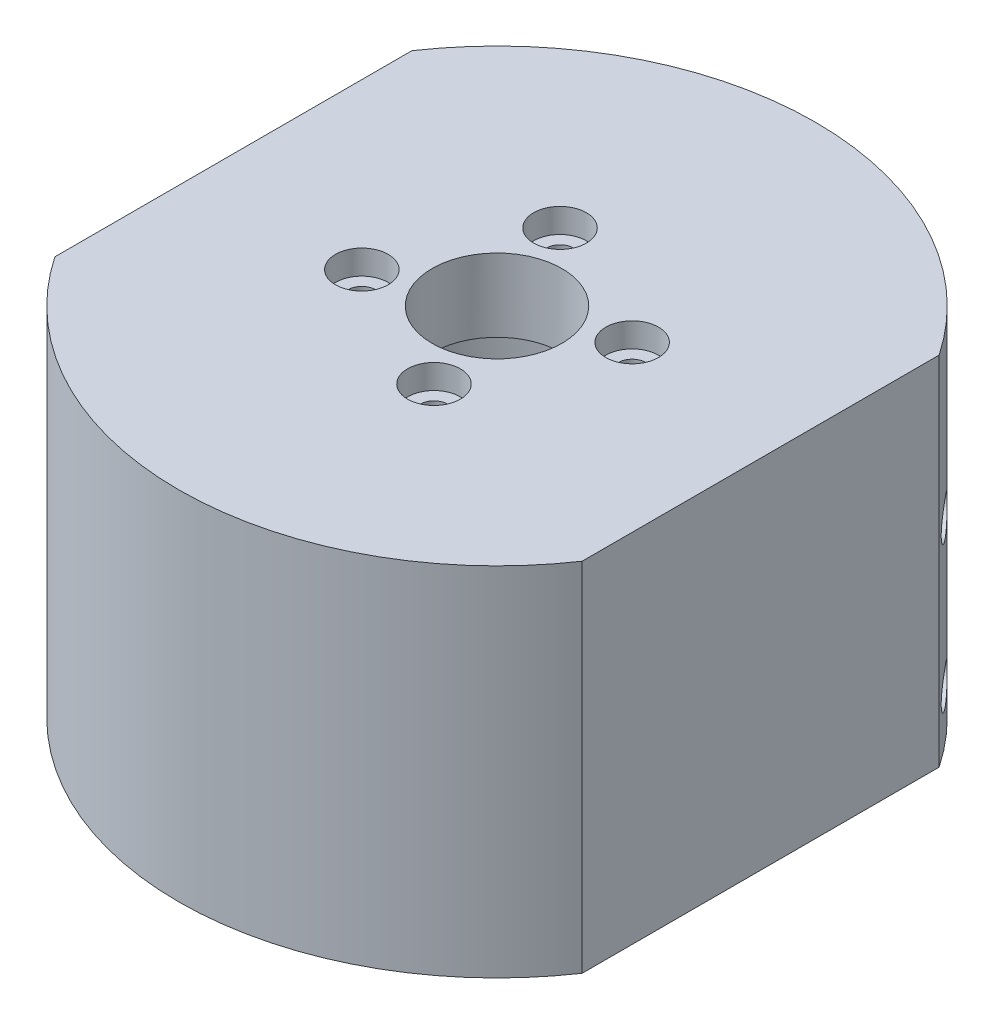
SolidWorks part; units mm, degrees
ref_plane "Front Plane" through (0, 0, 0) normal (0, 0, 1) x (1, 0, 0)
ref_plane "Top Plane" through (0, 0, 0) normal (0, 1, 0) x (1, 0, 0)
ref_plane "Right Plane" through (0, 0, 0) normal (1, 0, 0) x (0, 0, -1)
sketch "Sketch1" plane through (0, 0, 0) normal (0, 1, 0) x (1, 0, 0)
  line L0 (-32.5, 20.1696) -> (-32.5, -20.1696)
  line L1 (32.5, 20.1696) -> (32.5, -20.1696)
  line L2 (-32.5, 0) -> (32.5, 0) construction
  arc A0 (-32.5, -20.1696) -> (32.5, -20.1696) centre (0, 0) ccw
  arc A1 (32.5, 20.1696) -> (-32.5, 20.1696) centre (0, 0) ccw
  point P9 (0, 0)
  dimension "D1" = 65
  dimension "D2" = 76.5
extrude "Boss-Extrude1" add sketch "Sketch1" along normal blind 44
sketch "Sketch2" plane through (0, 44, 0) normal (0, 1, 0) x (1, 0, 0)
  line L0 (-4.4463, 12.216) -> (0, 0) construction
  line L1 (0, 13) -> (0, 0) construction
  circle A0 centre (0, 0) radius 13
  point P3 (-4.4463, 12.216)
  dimension "D1" = 26
  dimension "D2" = 20
hole_wizard "CBORE for M3 SHCS1" positions "Sketch2" profile "Sketch3" counterbore size "M3" standard "ANSI Metric" end condition through all
sketch "Sketch3" plane through (-4.4463, 44, -12.216) normal (1, 0, 0) x (0, 0, 1)
  line L0 (0, 0) -> (0, 44)
  line L1 (0, 44) -> (1.7, 44)
  line L3 (1.7, 44) -> (1.7, 3)
  line L4 (1.7, 3) -> (3.25, 3)
  line L5 (3.25, 3) -> (3.25, 0)
  line L7 (3.25, 0) -> (0, 0)
  line L11 (0, -6.35) -> (0, 107.95) construction
  dimension "Thru Hole Dia." = 3.4
  dimension "Thru Hole Depth" = 44
  dimension "C'Bore Dia." = 6.5
  dimension "C'Bore Depth" = 3
ref_axis "Axis1" through (0, 44, 0) along (0, -1, 0)
pattern_circular "CirPattern1" count 4 every 90 about axis through (0, 44, 0) along (0, -1, 0) of "CBORE for M3 SHCS1"
sketch "Sketch4" plane through (0, 0, 0) normal (0, -1, 0) x (1, 0, 0)
  circle A0 centre (0, 0) radius 16.2
  dimension "D1" = 32.4
extrude "Cut-Extrude1" cut sketch "Sketch4" against normal blind 35
sketch "Sketch5" plane through (0, 44, 0) normal (0, 1, 0) x (1, 0, 0)
  circle A0 centre (0, 0) radius 8
  dimension "D1" = 16
extrude "Cut-Extrude2" cut sketch "Sketch5" against normal through all
ref_plane "Plane1" through (0, 0, -38.25) normal (0, 0, -1) x (-1, 0, 0)
sketch "Sketch6" plane through (0, 0, -38.25) normal (0, 0, -1) x (-1, 0, 0)
  line L0 (-32.5, 44) -> (-32.5, 0) construction
  line L1 (-32.5, 0) -> (32.5, 0) construction
  circle A0 centre (-23.4, 6.85) radius 1.7
  dimension "D1" = 9.1
  dimension "D2" = 6.85
sketch "Sketch7" plane through (0, 0, 0) normal (0, -1, 0) x (1, 0, 0)
  line L0 (0, 38.25) -> (0, 39.25) construction
  line L1 (-32.5, 20.1696) -> (-32.5, 22.0071)
  line L2 (32.5, 20.1696) -> (32.5, 22.0071)
  line L3 (32.5, -20.1696) -> (32.5, -22.0071)
  line L4 (-32.5, -20.1696) -> (-32.5, -22.0071)
  arc A0 (-32.5, -20.1696) -> (32.5, -20.1696) centre (0, 0) ccw construction
  arc A1 (32.5, 20.1696) -> (-32.5, 20.1696) centre (0, 0) ccw construction
  arc A2 (-32.5, -20.1696) -> (32.5, -20.1696) centre (0, 0) ccw
  arc A3 (32.5, 20.1696) -> (-32.5, 20.1696) centre (0, 0) ccw
  circle A4 centre (0, 0) radius 39.25 construction
  arc A5 (-32.5, -22.0071) -> (32.5, -22.0071) centre (0, 0) ccw
  arc A6 (-32.5, 22.0071) -> (32.5, 22.0071) centre (0, 0) cw
  dimension "D1" = 1
extrude "Boss-Extrude2" add sketch "Sketch7" against normal up to surface (44 mm away) up to face at (0, 44, 8)
hole_wizard "CBORE for M4 SHCS1" positions "Sketch11" profile "Sketch12" counterbore size "M4" standard "ANSI Metric"
sketch "Sketch11" plane through (-50.0506, 499.7242, -401.677) normal (-1, 0, 0) x (0, -0.9859, -0.1676)
  line L0 (405.8768, 451.0689) -> (423.6223, 454.0852) construction
  line L2 (414.7496, 452.577) -> (416.4253, 442.7184) construction
  circle A0 centre (405.8768, 451.0689) radius 2.25
  circle A1 centre (423.6223, 454.0852) radius 2.25
  point P0 (405.8768, 451.0689)
  point P2 (423.6223, 454.0852)
sketch "Sketch12" plane through (-50.0506, 24, -25) normal (0, 1, 0) x (0, 0, 1)
  line L0 (0, 0) -> (0, 101.393)
  line L1 (0, 101.393) -> (2.15, 100.1012)
  line L2 (2.15, 100.1012) -> (2.15, 4)
  line L3 (2.15, 4) -> (4, 4)
  line L4 (4, 4) -> (4, 0)
  line L5 (4, 0) -> (0, 0)
  line L6 (0, 101.393) -> (-2.15, 100.1012) construction
  line L7 (0, -6.35) -> (0, 107.95) construction
  dimension "Hole Dia." = 4.3
  dimension "Hole Depth" = 100.1012
  dimension "C'Bore Dia." = 8
  dimension "C'Bore Depth" = 4
  dimension "Drill Angle" = 118
